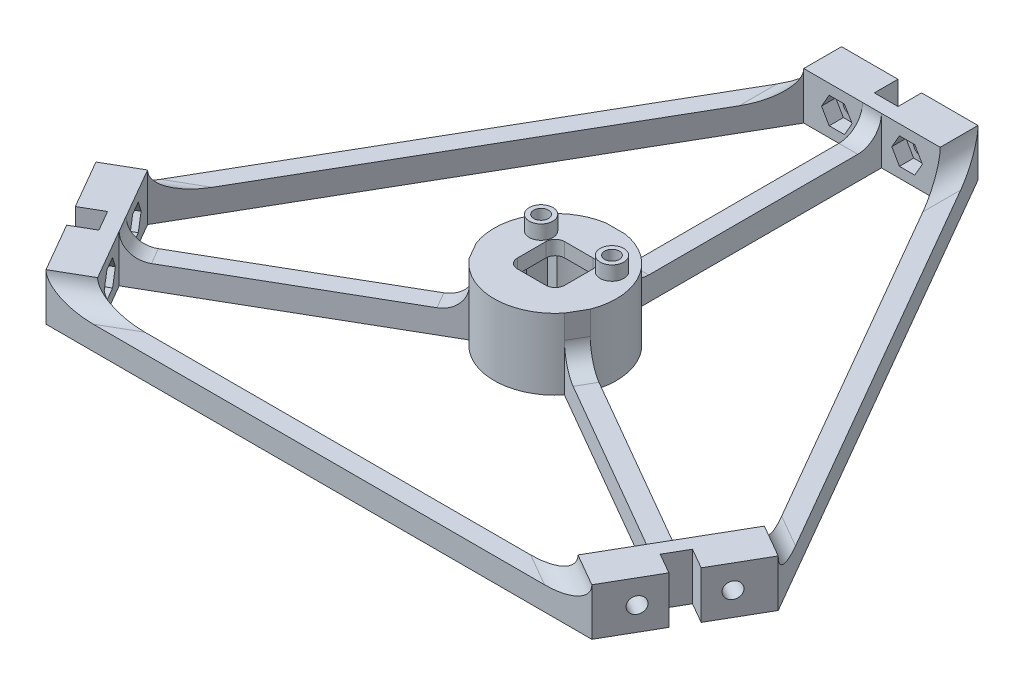
SolidWorks part; units mm, degrees
ref_plane "Front" through (0, 0, 0) normal (0, 0, 1) x (1, 0, 0)
ref_plane "Top" through (0, 0, 0) normal (0, 1, 0) x (1, 0, 0)
ref_plane "Right" through (0, 0, 0) normal (1, 0, 0) x (0, 0, -1)
sketch "Sketch1" plane through (0, 0, 0) normal (0, 1, 0) x (1, 0, 0)
  line L1 (-14.4338, 75) -> (-72.1688, -25)
  line L2 (-57.735, -50) -> (57.735, -50)
  line L3 (72.1688, -25) -> (14.4338, 75)
  line L4 (57.735, -50) -> (72.1688, -25)
  line L5 (14.4338, 75) -> (-14.4338, 75)
  line L6 (-72.1688, -25) -> (-57.735, -50)
  circle A2 centre (0, 0) radius 50 construction
  circle A3 centre (0, 0) radius 75 construction
  dimension "D1" = 100
  dimension "D2" = 150
extrude "Boss-Extrude1" add sketch "Sketch1" along normal blind 15
hole_wizard "M3 Clearance Hole1" positions "3DSketch1" profile "Sketch2" hole size "M3" standard "ANSI Metric"
sketch3d "3DSketch1"
  line L0 (57.735, 0, 50) -> (72.1688, 0, 25) construction
  line L1 (57.735, 15, 50) -> (57.735, 0, 50) construction
  line L2 (72.1688, 15, 25) -> (72.1688, 0, 25) construction
  point P0 (61.235, 5, 43.9378)
  point P2 (68.6688, 5, 31.0622)
  dimension "D1" = 5
  dimension "D2" = 7
  dimension "D3" = 5
  dimension "D4" = 7
sketch "Sketch2" plane through (61.235, 5, 43.9378) normal (0, 1, 0) x (0.5, 0, -0.866)
  line L0 (0, 0) -> (0, 25)
  line L1 (0, 25) -> (1.7, 23.9785)
  line L2 (1.7, 23.9785) -> (1.7, 0)
  line L5 (1.7, 0) -> (0, 0)
  line L10 (0, 25) -> (-1.7, 23.9785) construction
  line L11 (0, -6.35) -> (0, 107.95) construction
  dimension "Hole Dia." = 3.4
  dimension "Hole Depth" = 25
  dimension "Drill Angle" = 118
hole_wizard "M3 Clearance Hole2" positions "3DSketch2" profile "Sketch3" hole size "M3" standard "ANSI Metric"
sketch3d "3DSketch2"
  line L0 (14.4338, 15, -75) -> (14.4338, 0, -75) construction
  line L1 (14.4338, 0, -75) -> (-14.4338, 0, -75) construction
  line L2 (-14.4338, 15, -75) -> (-14.4338, 0, -75) construction
  point P0 (7.4338, 5, -75)
  point P2 (-7.4338, 5, -75)
  dimension "D1" = 7
  dimension "D2" = 5
  dimension "D3" = 5
  dimension "D4" = 7
sketch "Sketch3" plane through (7.4338, 5, -75) normal (1, 0, 0) x (0, 1, 0)
  line L0 (0, 0) -> (0, 25)
  line L1 (0, 25) -> (1.7, 23.9785)
  line L2 (1.7, 23.9785) -> (1.7, 0)
  line L5 (1.7, 0) -> (0, 0)
  line L10 (0, 25) -> (-1.7, 23.9785) construction
  line L11 (0, -6.35) -> (0, 107.95) construction
  dimension "Hole Dia." = 3.4
  dimension "Hole Depth" = 25
  dimension "Drill Angle" = 118
hole_wizard "M3 Clearance Hole3" positions "3DSketch3" profile "Sketch4" hole size "M3" standard "ANSI Metric"
sketch3d "3DSketch3"
  line L0 (-72.1688, 15, 25) -> (-72.1688, 0, 25) construction
  line L1 (-72.1688, 0, 25) -> (-57.735, 0, 50) construction
  line L2 (-57.735, 15, 50) -> (-57.735, 0, 50) construction
  point P0 (-68.6688, 5, 31.0622)
  point P2 (-61.235, 5, 43.9378)
  dimension "D1" = 7
  dimension "D2" = 5
  dimension "D3" = 5
  dimension "D4" = 7
sketch "Sketch4" plane through (-68.6688, 5, 31.0622) normal (0, 1, 0) x (0.5, 0, 0.866)
  line L0 (0, 0) -> (0, 25)
  line L1 (0, 25) -> (1.7, 23.9785)
  line L2 (1.7, 23.9785) -> (1.7, 0)
  line L5 (1.7, 0) -> (0, 0)
  line L10 (0, 25) -> (-1.7, 23.9785) construction
  line L11 (0, -6.35) -> (0, 107.95) construction
  dimension "Hole Dia." = 3.4
  dimension "Hole Depth" = 25
  dimension "Drill Angle" = 118
sketch "Sketch5" plane through (-64.9519, 0, 37.5) normal (-0.866, 0, 0.5) x (0.5, 0, 0.866)
  line L6 (0, 15) -> (0, 0) construction
  line L7 (-14.4338, 15) -> (14.4338, 15) construction
  line L8 (-14.4338, 0) -> (14.4338, 0) construction
  line L10 (-2.5, 15) -> (2.5, 15)
  line L11 (-2.5, 15) -> (-2.5, 0)
  line L12 (-2.5, 0) -> (2.5, 0)
  line L13 (2.5, 15) -> (2.5, 0)
  dimension "D1" = 2.5
  dimension "D2" = 2.5
extrude "Cut-Extrude1" cut sketch "Sketch5" against normal blind 5
sketch "Sketch6" plane through (64.9519, 0, 37.5) normal (0.866, 0, 0.5) x (0.5, 0, -0.866)
  line L0 (0, 15) -> (0, 0) construction
  line L1 (-14.4338, 15) -> (14.4338, 15) construction
  line L2 (-14.4338, 0) -> (14.4338, 0) construction
  line L4 (-2.5, 15) -> (2.5, 15)
  line L5 (-2.5, 15) -> (-2.5, 0)
  line L6 (-2.5, 0) -> (2.5, 0)
  line L7 (2.5, 15) -> (2.5, 0)
  dimension "D1" = 2.5
  dimension "D2" = 2.5
extrude "Cut-Extrude2" cut sketch "Sketch6" against normal blind 5
sketch "Sketch7" plane through (0, 0, -75) normal (0, 0, -1) x (-1, 0, 0)
  line L0 (0, 15) -> (0, 0) construction
  line L1 (-14.4338, 15) -> (14.4338, 15) construction
  line L2 (-14.4338, 0) -> (14.4338, 0) construction
  line L4 (-2.5, 15) -> (2.5, 15)
  line L5 (-2.5, 15) -> (-2.5, 0)
  line L6 (-2.5, 0) -> (2.5, 0)
  line L7 (2.5, 15) -> (2.5, 0)
  dimension "D1" = 2.5
  dimension "D2" = 2.5
extrude "Cut-Extrude3" cut sketch "Sketch7" against normal blind 5
sketch "Sketch8" plane through (0, 15, 0) normal (0, 1, 0) x (1, 0, 0)
  line L0 (65.2406, -21) -> (14.4338, 67)
  line L1 (14.4338, 67) -> (2, 67)
  line L2 (-14.4338, 67) -> (-65.2406, -21)
  line L3 (-65.2406, -21) -> (-59.0237, -31.7679)
  line L4 (-50.8068, -46) -> (50.8068, -46)
  line L5 (50.8068, -46) -> (57.0237, -35.2321)
  line L7 (-14.4338, 75) -> (-72.1688, -25) construction
  line L8 (-2.5, 75) -> (-14.4338, 75) construction
  line L9 (72.1688, -25) -> (14.4338, 75) construction
  line L10 (66.2019, -35.3349) -> (72.1688, -25) construction
  line L11 (-57.735, -50) -> (57.735, -50) construction
  line L12 (-63.7019, -39.6651) -> (-57.735, -50) construction
  line L13 (0, 70) -> (0, -50) construction
  line L14 (-2.5, 70) -> (2.5, 70) construction
  line L15 (60.6218, -35) -> (-43.3013, 25) construction
  line L16 (61.8718, -32.8349) -> (59.3718, -37.1651) construction
  line L17 (-60.6218, -35) -> (43.3013, 25) construction
  line L18 (-59.3718, -37.1651) -> (-61.8718, -32.8349) construction
  line L19 (-59.0237, -31.7679) -> (-12.0711, -4.6599)
  line L20 (-57.0237, -35.2321) -> (-10.0711, -8.124)
  line L21 (2, 67) -> (2, 12.7838)
  line L22 (-2, 67) -> (-2, 12.7838)
  line L23 (59.0237, -31.7679) -> (12.0711, -4.6599)
  line L24 (57.0237, -35.2321) -> (10.0711, -8.124)
  line L25 (59.0237, -31.7679) -> (65.2406, -21)
  line L26 (-2, 67) -> (-14.4338, 67)
  line L27 (-57.0237, -35.2321) -> (-50.8068, -46)
  arc A0 (12.0711, -4.6599) -> (2, 12.7838) centre (0, 0) ccw
  arc A1 (-2, 12.7838) -> (-12.0711, -4.6599) centre (0, 0) ccw
  arc A2 (-10.0711, -8.124) -> (10.0711, -8.124) centre (0, 0) ccw
  dimension "D7" = 2
  dimension "D1" = 4
  dimension "D2" = 4
  dimension "D3" = 4
  dimension "D4" = 8
  dimension "D5" = 8
  dimension "D6" = 8
  dimension "D8" = 2
  dimension "D9" = 2
  dimension "D10" = 2
  dimension "D11" = 2
  dimension "D12" = 2
extrude "Cut-Extrude4" cut sketch "Sketch8" against normal up to next
sketch "Sketch9" plane through (0, 15, 0) normal (0, 1, 0) x (1, 0, 0)
  line L0 (14.4338, 75) -> (14.4338, 67)
  line L1 (14.4338, 67) -> (65.2406, -21)
  line L2 (65.2406, -21) -> (72.1688, -25)
  line L3 (72.1688, -25) -> (14.4338, 75)
  line L4 (57.735, -50) -> (50.8068, -46)
  line L5 (50.8068, -46) -> (-50.8068, -46)
  line L6 (-50.8068, -46) -> (-57.735, -50)
  line L7 (-57.735, -50) -> (57.735, -50)
  line L8 (-14.4338, 75) -> (-14.4338, 67)
  line L9 (-14.4338, 67) -> (-65.2406, -21)
  line L10 (-65.2406, -21) -> (-72.1688, -25)
  line L11 (-72.1688, -25) -> (-14.4338, 75)
  line L12 (-2, 67) -> (2, 67)
  line L13 (2, 67) -> (2, 12.7838)
  line L14 (2, 12.7838) -> (-2, 12.7838)
  line L15 (-2, 12.7838) -> (-2, 67)
  line L16 (-10.0711, -8.124) -> (-57.0237, -35.2321)
  line L17 (-57.0237, -35.2321) -> (-59.0237, -31.7679)
  line L18 (-59.0237, -31.7679) -> (-12.0711, -4.6599)
  line L19 (-12.0711, -4.6599) -> (-10.0711, -8.124)
  line L20 (59.0237, -31.7679) -> (57.0237, -35.2321)
  line L21 (57.0237, -35.2321) -> (10.0711, -8.124)
  line L22 (10.0711, -8.124) -> (12.0711, -4.6599)
  line L23 (12.0711, -4.6599) -> (59.0237, -31.7679)
extrude "Cut-Extrude5" cut sketch "Sketch9" against normal blind 10
fillet "Fillet1" radius 5 12 edges at (11.0711, 5, 6.3919) (58.0237, 5, 33.5) (0, 5, -67) (0, 5, -12.7838) (-68.7047, 5, 23) (-14.4338, 5, -71) (14.4338, 5, -71) (68.7047, 5, 23) (54.2709, 5, 48) (-54.2709, 5, 48) (-58.0237, 5, 33.5) (-11.0711, 5, 6.3919)
sketch "Sketch10" plane through (0, 0, -67) normal (0, 0, 1) x (1, 0, 0)
  line L2 (-10.6669, 5) -> (-9.0503, 2.2)
  line L3 (-9.0503, 2.2) -> (-5.8172, 2.2)
  line L4 (-5.8172, 2.2) -> (-4.2006, 5)
  line L5 (-4.2006, 5) -> (-5.8172, 7.8)
  line L6 (-5.8172, 7.8) -> (-9.0503, 7.8)
  line L7 (-9.0503, 7.8) -> (-10.6669, 5)
  circle A0 centre (-7.4338, 5) radius 2.8 construction
  dimension "D1" = 5.6
extrude "Cut-Extrude6" cut sketch "Sketch10" against normal blind 3
sketch "Sketch11" plane through (0, 0, -67) normal (0, 0, 1) x (1, 0, 0)
  line L1 (4.2006, 5) -> (5.8172, 2.2)
  line L2 (5.8172, 2.2) -> (9.0503, 2.2)
  line L3 (9.0503, 2.2) -> (10.6669, 5)
  line L4 (10.6669, 5) -> (9.0503, 7.8)
  line L5 (9.0503, 7.8) -> (5.8172, 7.8)
  line L6 (5.8172, 7.8) -> (4.2006, 5)
  circle A0 centre (7.4338, 5) radius 2.8 construction
  dimension "D1" = 5.6
extrude "Cut-Extrude7" cut sketch "Sketch11" against normal blind 3
sketch "Sketch12" plane through (58.0237, 0, 33.5) normal (-0.866, 0, -0.5) x (-0.5, 0, 0.866)
  line L1 (-10.6669, 5) -> (-9.0503, 2.2)
  line L2 (-9.0503, 2.2) -> (-5.8172, 2.2)
  line L3 (-5.8172, 2.2) -> (-4.2006, 5)
  line L4 (-4.2006, 5) -> (-5.8172, 7.8)
  line L5 (-5.8172, 7.8) -> (-9.0503, 7.8)
  line L6 (-9.0503, 7.8) -> (-10.6669, 5)
  line L7 (4.2006, 5) -> (5.8172, 2.2)
  line L8 (5.8172, 2.2) -> (9.0503, 2.2)
  line L9 (9.0503, 2.2) -> (10.6669, 5)
  line L10 (10.6669, 5) -> (9.0503, 7.8)
  line L11 (9.0503, 7.8) -> (5.8172, 7.8)
  line L12 (5.8172, 7.8) -> (4.2006, 5)
  circle A0 centre (-7.4338, 5) radius 2.8 construction
  circle A1 centre (7.4338, 5) radius 2.8 construction
  dimension "D1" = 5.6
  dimension "D2" = 5.6
extrude "Cut-Extrude8" cut sketch "Sketch12" against normal blind 3
sketch "Sketch13" plane through (-58.0237, 0, 33.5) normal (0.866, 0, -0.5) x (-0.5, 0, -0.866)
  line L1 (-10.6669, 5) -> (-9.0503, 2.2)
  line L2 (-9.0503, 2.2) -> (-5.8172, 2.2)
  line L3 (-5.8172, 2.2) -> (-4.2006, 5)
  line L4 (-4.2006, 5) -> (-5.8172, 7.8)
  line L5 (-5.8172, 7.8) -> (-9.0503, 7.8)
  line L6 (-9.0503, 7.8) -> (-10.6669, 5)
  line L7 (4.2006, 5) -> (5.8172, 2.2)
  line L8 (5.8172, 2.2) -> (9.0503, 2.2)
  line L9 (9.0503, 2.2) -> (10.6669, 5)
  line L10 (10.6669, 5) -> (9.0503, 7.8)
  line L11 (9.0503, 7.8) -> (5.8172, 7.8)
  line L12 (5.8172, 7.8) -> (4.2006, 5)
  circle A0 centre (-7.4338, 5) radius 2.8 construction
  circle A1 centre (7.4338, 5) radius 2.8 construction
  dimension "D1" = 5.6
  dimension "D2" = 5.6
extrude "Cut-Extrude9" cut sketch "Sketch13" against normal blind 3
sketch "Sketch14" plane through (0, 15, 0) normal (0, 1, 0) x (1, 0, 0)
  line L0 (-72.1688, -25) -> (-65.2406, -21)
  line L1 (-65.2406, -21) -> (-50.8068, -46)
  line L2 (-50.8068, -46) -> (-57.735, -50)
  line L3 (-57.735, -50) -> (-72.1688, -25)
  line L4 (-14.4338, 75) -> (-14.4338, 67)
  line L5 (-14.4338, 67) -> (14.4338, 67)
  line L6 (14.4338, 67) -> (14.4338, 75)
  line L7 (14.4338, 75) -> (-14.4338, 75)
  line L8 (65.2406, -21) -> (72.1688, -25)
  line L9 (72.1688, -25) -> (57.735, -50)
  line L10 (57.735, -50) -> (50.8068, -46)
  line L11 (57.735, -50) -> (50.8068, -46) construction
  line L12 (50.8068, -46) -> (65.2406, -21) construction
  line L13 (50.8068, -46) -> (65.2406, -21)
extrude "Cut-Extrude10" cut sketch "Sketch14" against normal up to vertex (5 mm away) up to point (-57.735, 10, 50)
sketch "Sketch15" plane through (0, 0, 0) normal (0, -1, 0) x (-1, 0, 0)
  circle A0 centre (0, 0) radius 10
  dimension "D1" = 20
extrude "Cut-Extrude11" cut sketch "Sketch15" against normal blind 12
sketch "Sketch16" plane through (0, 15, 0) normal (0, 1, 0) x (1, 0, 0)
  line L3 (-3, -5) -> (3, -5)
  line L4 (-5, -3) -> (-5, 3)
  line L5 (-3, 5) -> (3, 5)
  line L6 (5, -3) -> (5, 3)
  line L7 (-5, -5) -> (5, 5) construction
  line L8 (-5, 5) -> (5, -5) construction
  arc A0 (-5, 3) -> (-3, 5) centre (-3, 3) cw
  arc A1 (-3, -5) -> (-5, -3) centre (-3, -3) cw
  arc A2 (3, -5) -> (5, -3) centre (3, -3) ccw
  arc A3 (3, 5) -> (5, 3) centre (3, 3) cw
  dimension "D3" = 2
  dimension "D1" = 10
  dimension "D2" = 10
extrude "Cut-Extrude12" cut sketch "Sketch16" against normal up to next
sketch "Sketch17" plane through (0, 15, 0) normal (0, 1, 0) x (1, 0, 0)
  circle A0 centre (7.5, 4.5) radius 1.55
  circle A1 centre (-7.5, 4.5) radius 1.55
  circle A2 centre (7.5, 4.5) radius 2.5
  circle A3 centre (-7.5, 4.5) radius 2.5
extrude "Boss-Extrude2" add sketch "Sketch17" along normal blind 3
sketch "Sketch18" plane through (0, 15, 0) normal (0, 1, 0) x (1, 0, 0)
  circle A0 centre (7.5, 4.5) radius 1.55
  circle A1 centre (-7.5, 4.5) radius 1.55
extrude "Cut-Extrude13" cut sketch "Sketch18" against normal up to next
sketch "Sketch19" plane through (0, 0, 0) normal (0, -1, 0) x (-1, 0, 0)
  line L1 (-10.7332, 4.5) -> (-9.1166, 1.7)
  line L2 (-9.1166, 1.7) -> (-5.8834, 1.7)
  line L3 (-5.8834, 1.7) -> (-4.2668, 4.5)
  line L4 (-4.2668, 4.5) -> (-5.8834, 7.3)
  line L5 (-5.8834, 7.3) -> (-9.1166, 7.3)
  line L6 (-9.1166, 7.3) -> (-10.7332, 4.5)
  line L7 (10.7289, 4.6653) -> (8.9713, 7.379)
  line L8 (8.9713, 7.379) -> (5.7424, 7.2137)
  line L9 (5.7424, 7.2137) -> (4.2711, 4.3347)
  line L10 (4.2711, 4.3347) -> (6.0287, 1.621)
  line L11 (6.0287, 1.621) -> (9.2576, 1.7863)
  line L12 (9.2576, 1.7863) -> (10.7289, 4.6653)
  circle A0 centre (-7.5, 4.5) radius 2.8 construction
  circle A1 centre (7.5, 4.5) radius 2.8 construction
  point P10 (-10.7332, 4.5)
  point P19 (8.8076, 7.4569)
  point P20 (10.7289, 4.6653)
  dimension "D1" = 5.6
  dimension "D2" = 5.6
extrude "Cut-Extrude14" cut sketch "Sketch19" against normal up to surface (12 mm away) up to face at (0, 12, -1.8513)
